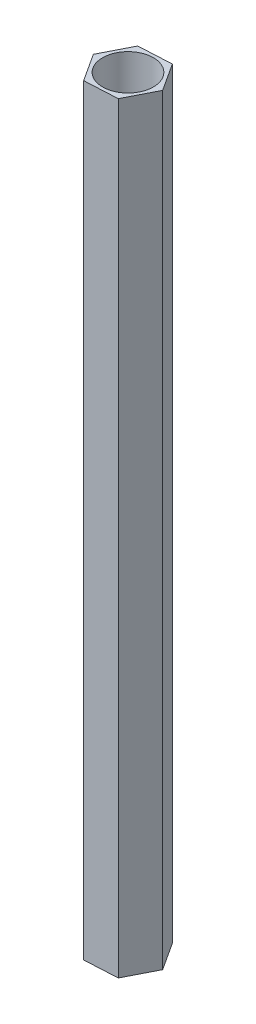
SolidWorks part; units mm, degrees
ref_plane "Front Plane" through (0, 0, 0) normal (0, 0, 1) x (1, 0, 0)
ref_plane "Top Plane" through (0, 0, 0) normal (0, 1, 0) x (1, 0, 0)
ref_plane "Right Plane" through (0, 0, 0) normal (1, 0, 0) x (0, 0, -1)
sketch "Sketch1" plane through (0, 0, 0) normal (0, 1, 0) x (1, 0, 0)
  line L1 (1.4133, -2.1801) -> (2.5946, 0.1339)
  line L2 (2.5946, 0.1339) -> (1.1813, 2.314)
  line L3 (1.1813, 2.314) -> (-1.4133, 2.1801)
  line L4 (-1.4133, 2.1801) -> (-2.5946, -0.1339)
  line L5 (-2.5946, -0.1339) -> (-1.1813, -2.314)
  line L6 (-1.1813, -2.314) -> (1.4133, -2.1801)
  circle A0 centre (0, 0) radius 2.25 construction
  circle A1 centre (0, 0) radius 2
  dimension "D1" = 4.5
  dimension "D2" = 4
extrude "Boss-Extrude1" add sketch "Sketch1" along normal blind 60
